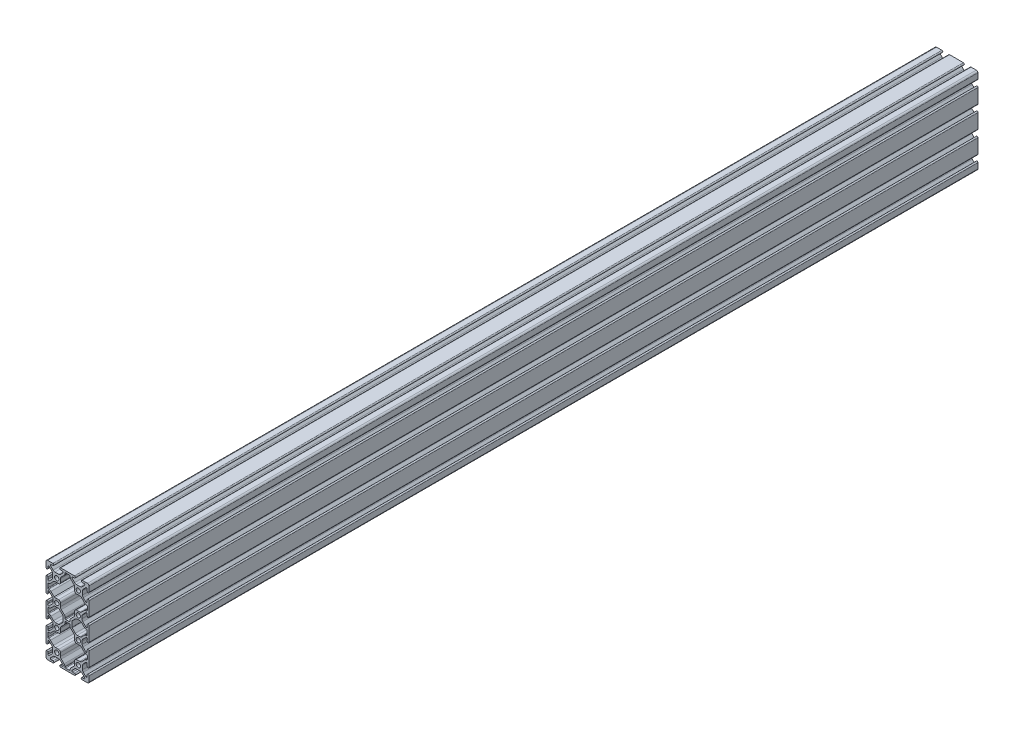
SolidWorks part; units mm, degrees
material "6061 Alloy"
ref_plane "Front Plane" through (0, 0, 0) normal (0, 0, 1) x (1, 0, 0)
ref_plane "Top Plane" through (0, 0, 0) normal (0, 1, 0) x (1, 0, 0)
ref_plane "Right Plane" through (0, 0, 0) normal (1, 0, 0) x (0, 0, -1)
sketch "Sketch1" plane through (0, 0, 0) normal (0, 0, 1) x (1, 0, 0)
  line L0 (-25.6036, 0) -> (0, 0) construction
  line L1 (-8.2025, 43.3108) -> (-5.2383, 46.275)
  line L2 (-25, 3.77) -> (-25, -3.77)
  line L3 (-8.1858, 12.4875) -> (-8.1858, 11.0114)
  line L4 (8.1878, 11.0114) -> (8.1878, 14.5891)
  line L5 (3.7569, 4.9667) -> (7.2705, 8.4802)
  line L6 (14.3225, 16.7991) -> (10.3978, 16.7991)
  line L7 (15.6024, 17.1021) -> (19.2982, 20.7979)
  line L8 (22.1127, 21.7264) -> (21.5397, 21.7264)
  line L9 (-2.3158, 50) -> (2.3158, 50)
  line L10 (22.8749, 26.8568) -> (22.8749, 22.4886)
  line L11 (21.8715, 27.6122) -> (22.1256, 27.6122)
  line L12 (19.7762, 28.7106) -> (16.3874, 32.0994)
  line L13 (13.8398, 33.0305) -> (10.3624, 33.0305)
  line L14 (8.1524, 39.0512) -> (8.1524, 35.2405)
  line L15 (7.2223, 41.2645) -> (4.0122, 44.4746)
  line L16 (3.0895, 47.0978) -> (3.0895, 46.7023)
  line L17 (-22.86, 2.484) -> (-22.86, -2.484)
  line L18 (-5.137, 3.0639) -> (-5.137, -3.0639)
  line L19 (5.137, 3.0639) -> (5.137, -3.0639)
  line L20 (22.86, 2.484) -> (22.86, -2.484)
  line L21 (-5.328, 3.5248) -> (-8.9952, 7.192)
  line L22 (-14.0474, 8.1222) -> (-11.2408, 8.1222)
  line L23 (-16.2931, 7.192) -> (-19.3292, 4.1559)
  line L24 (25, 3.77) -> (25, -3.77)
  line L25 (-22.0978, 3.2462) -> (-21.8437, 3.2462)
  line L26 (-10.3899, 33.0305) -> (-10.3624, 33.0305)
  line L27 (-8.1858, 12.4875) -> (-8.1858, 14.5891)
  line L28 (-8.1524, 39.0512) -> (-8.1524, 35.2405)
  line L29 (-25.6036, -25) -> (3.1162, -25) construction
  line L30 (-12.5, -37.5) -> (-12.5, -51.8721) construction
  line L31 (8.2025, -43.3108) -> (5.2383, -46.275)
  line L32 (-2.8325, -2.6943) -> (-2.8325, -1.8197)
  line L33 (-2.0703, -1.0575) -> (2.0723, -1.0575)
  line L34 (2.8345, -2.6943) -> (2.8345, -1.8197)
  line L35 (-3.7549, -4.9667) -> (-7.2685, -8.4802)
  line L36 (-14.3205, -16.7991) -> (-10.3958, -16.7991)
  line L37 (-15.6004, -17.1021) -> (-19.2962, -20.7979)
  line L38 (-22.1107, -21.7264) -> (-21.5377, -21.7264)
  line L39 (-22.8729, -26.8568) -> (-22.8729, -22.4886)
  line L40 (-22.1107, -27.619) -> (-21.8566, -27.619)
  line L41 (5.328, -3.5248) -> (8.9952, -7.192)
  line L42 (11.2408, -8.1222) -> (14.0474, -8.1222)
  line L43 (16.2931, -7.192) -> (19.3292, -4.1559)
  line L44 (-19.7762, -28.7106) -> (-16.3874, -32.0994)
  line L45 (22.0978, -3.2462) -> (21.8437, -3.2462)
  line L46 (-13.8398, -33.0305) -> (-10.3899, -33.0305)
  line L47 (-7.2223, -41.2645) -> (-4.0122, -44.4746)
  line L48 (5.8948, -47.86) -> (8.0244, -47.86)
  line L49 (-8.0244, 50) -> (-2.3158, 50)
  line L50 (-8.0244, 47.86) -> (-5.8948, 47.86)
  line L51 (0, 47.86) -> (2.3273, 47.86)
  line L52 (-3.0895, -47.0978) -> (-3.0895, -46.7023)
  line L53 (-14.7082, 42.4485) -> (-10.2843, 42.4484)
  line L54 (-16.7975, 43.3108) -> (-19.7617, 46.275)
  line L55 (-19.1052, 47.86) -> (-16.9756, 47.86)
  line L56 (-23.0411, 50) -> (-16.9756, 50)
  line L57 (2.3158, 50) -> (8.0244, 50)
  line L58 (-25, 42.0822) -> (-25, 48.3182)
  line L59 (10.2843, -42.4484) -> (14.7082, -42.4485)
  line L60 (-22.86, 42.0822) -> (-22.86, 44.2118)
  line L61 (-21.1643, 44.6511) -> (-18.3279, 41.8147)
  line L62 (-17.3977, 39.5691) -> (-17.3977, 35.4309)
  line L63 (-18.3279, 33.1853) -> (-21.1271, 30.3861)
  line L64 (-22.86, 31.1039) -> (-22.86, 33.4422)
  line L65 (-25, 33.4422) -> (-25, 29.299)
  line L66 (-25, 21.2197) -> (-25, 29.299)
  line L67 (-25, 17.0404) -> (-25, 21.2197)
  line L68 (-22.8665, 17.0958) -> (-22.8665, 19.4894)
  line L69 (-21.2483, 19.7351) -> (-17.927, 16.4138)
  line L70 (-16.865, 11.3738) -> (-16.865, 14.4803)
  line L71 (-17.7378, 8.7737) -> (-21.0608, 5.4507)
  line L72 (-22.8659, 6.4893) -> (-22.8659, 8.2661)
  line L73 (-25, 3.77) -> (-25, 8.2776)
  line L74 (16.7975, -43.3108) -> (19.7617, -46.275)
  line L75 (19.1052, -47.86) -> (16.9756, -47.86)
  line L76 (16.9756, -50) -> (21.7588, -50)
  line L77 (21.7588, -50) -> (23.0411, -50)
  line L78 (25, -42.0822) -> (25, -48.3182)
  line L79 (22.86, -42.0822) -> (22.86, -44.2118)
  line L80 (21.1643, -44.6511) -> (18.3279, -41.8147)
  line L81 (17.3977, -39.5691) -> (17.3977, -35.4309)
  line L82 (18.3279, -33.1853) -> (21.1271, -30.3861)
  line L83 (25, -33.4422) -> (25, -29.299)
  line L84 (22.86, -31.1039) -> (22.86, -33.4422)
  line L85 (-2.3273, -47.86) -> (0, -47.86)
  line L86 (22.8665, -17.0958) -> (22.8665, -19.4894)
  line L87 (21.2483, -19.7351) -> (17.927, -16.4138)
  line L88 (16.865, -11.3738) -> (16.865, -14.4803)
  line L89 (17.7378, -8.7737) -> (21.0608, -5.4507)
  line L90 (22.8659, -6.4893) -> (22.8659, -8.2661)
  line L91 (25, -21.2197) -> (25, -29.299)
  line L92 (25, -17.0404) -> (25, -21.2197)
  line L93 (25, -3.77) -> (25, -8.2776)
  line L94 (-25, -3.77) -> (-25, -8.2776)
  line L95 (-12.5, 37.5) -> (-12.5, 51.8721) construction
  line L96 (-25.6036, 25) -> (3.1162, 25) construction
  line L97 (-22.8659, -6.4893) -> (-22.8659, -8.2661)
  line L98 (-17.7378, -8.7737) -> (-21.0608, -5.4507)
  line L99 (-16.865, -11.3738) -> (-16.865, -14.4803)
  line L100 (-21.2483, -19.7351) -> (-17.927, -16.4138)
  line L101 (-22.8665, -17.0958) -> (-22.8665, -19.4894)
  line L102 (-25, -17.0404) -> (-25, -21.2197)
  line L103 (-25, -21.2197) -> (-25, -29.299)
  line L104 (-25, -33.4422) -> (-25, -29.299)
  line L105 (-22.86, -31.1039) -> (-22.86, -33.4422)
  line L106 (25, 3.77) -> (25, 8.2776)
  line L107 (25, 17.0404) -> (25, 21.2197)
  line L108 (-18.3279, -33.1853) -> (-21.1271, -30.3861)
  line L109 (-17.3977, -39.5691) -> (-17.3977, -35.4309)
  line L110 (-21.1643, -44.6511) -> (-18.3279, -41.8147)
  line L111 (-22.86, -42.0822) -> (-22.86, -44.2118)
  line L112 (-25, -42.0822) -> (-25, -48.3182)
  line L113 (25, 21.2197) -> (25, 29.299)
  line L114 (2.3158, -50) -> (8.0244, -50)
  line L115 (-23.0411, -50) -> (-16.9756, -50)
  line L116 (22.8659, 6.4893) -> (22.8659, 8.2661)
  line L117 (17.7378, 8.7737) -> (21.0608, 5.4507)
  line L118 (16.865, 11.3738) -> (16.865, 14.4803)
  line L119 (21.2483, 19.7351) -> (17.927, 16.4138)
  line L120 (22.8665, 17.0958) -> (22.8665, 19.4894)
  line L121 (-2.3273, 47.86) -> (0, 47.86)
  line L122 (22.86, 31.1039) -> (22.86, 33.4422)
  line L123 (25, 33.4422) -> (25, 29.299)
  line L124 (-19.1052, -47.86) -> (-16.9756, -47.86)
  line L125 (18.3279, 33.1853) -> (21.1271, 30.3861)
  line L126 (17.3977, 39.5691) -> (17.3977, 35.4309)
  line L127 (21.1643, 44.6511) -> (18.3279, 41.8147)
  line L128 (22.86, 42.0822) -> (22.86, 44.2118)
  line L129 (25, 42.0822) -> (25, 48.3182)
  line L130 (-16.7975, -43.3108) -> (-19.7617, -46.275)
  line L131 (21.7588, 50) -> (23.0411, 50)
  line L132 (16.9756, 50) -> (21.7588, 50)
  line L133 (19.1052, 47.86) -> (16.9756, 47.86)
  line L134 (16.7975, 43.3108) -> (19.7617, 46.275)
  line L135 (10.2843, 42.4484) -> (14.7082, 42.4485)
  line L136 (-14.7082, -42.4485) -> (-10.2843, -42.4484)
  line L137 (-3.0895, 47.0978) -> (-3.0895, 46.7023)
  line L138 (5.8948, 47.86) -> (8.0244, 47.86)
  line L139 (0, -47.86) -> (2.3273, -47.86)
  line L140 (-8.0244, -47.86) -> (-5.8948, -47.86)
  line L141 (-8.0244, -50) -> (-2.3158, -50)
  line L142 (-8.1524, -39.0512) -> (-8.1524, -35.2405)
  line L143 (-8.1858, -12.4875) -> (-8.1858, -14.5891)
  line L144 (-10.3899, -33.0305) -> (-10.3624, -33.0305)
  line L145 (-22.0978, -3.2462) -> (-21.8437, -3.2462)
  line L146 (-16.2931, -7.192) -> (-19.3292, -4.1559)
  line L147 (-14.0474, -8.1222) -> (-11.2408, -8.1222)
  line L148 (-5.328, -3.5248) -> (-8.9952, -7.192)
  line L149 (3.0895, -47.0978) -> (3.0895, -46.7023)
  line L150 (7.2223, -41.2645) -> (4.0122, -44.4746)
  line L151 (8.1524, -39.0512) -> (8.1524, -35.2405)
  line L152 (13.8398, -33.0305) -> (10.3624, -33.0305)
  line L153 (19.7762, -28.7106) -> (16.3874, -32.0994)
  line L154 (-7.2223, 41.2645) -> (-4.0122, 44.4746)
  line L155 (21.8715, -27.6122) -> (22.1256, -27.6122)
  line L156 (22.8749, -26.8568) -> (22.8749, -22.4886)
  line L157 (-2.3158, -50) -> (2.3158, -50)
  line L158 (22.1127, -21.7264) -> (21.5397, -21.7264)
  line L159 (15.6024, -17.1021) -> (19.2982, -20.7979)
  line L160 (-13.8398, 33.0305) -> (-10.3899, 33.0305)
  line L161 (14.3225, -16.7991) -> (10.3978, -16.7991)
  line L162 (22.0978, 3.2462) -> (21.8437, 3.2462)
  line L163 (-19.7762, 28.7106) -> (-16.3874, 32.0994)
  line L164 (16.2931, 7.192) -> (19.3292, 4.1559)
  line L165 (11.2408, 8.1222) -> (14.0474, 8.1222)
  line L166 (5.328, 3.5248) -> (8.9952, 7.192)
  line L167 (3.7569, -4.9667) -> (7.2705, -8.4802)
  line L168 (8.1878, -11.0114) -> (8.1878, -14.5891)
  line L169 (-8.1858, -12.4875) -> (-8.1858, -11.0114)
  line L170 (-8.2025, -43.3108) -> (-5.2383, -46.275)
  line L171 (-22.1107, 27.619) -> (-21.8566, 27.619)
  line L172 (-22.8729, 26.8568) -> (-22.8729, 22.4886)
  line L173 (-22.1107, 21.7264) -> (-21.5377, 21.7264)
  line L174 (-15.6004, 17.1021) -> (-19.2962, 20.7979)
  line L175 (-14.3205, 16.7991) -> (-10.3958, 16.7991)
  line L176 (-3.7549, 4.9667) -> (-7.2685, 8.4802)
  line L177 (2.8345, 2.6943) -> (2.8345, 1.8197)
  line L178 (-2.0703, 1.0575) -> (2.0723, 1.0575)
  line L179 (-2.8325, 2.6943) -> (-2.8325, 1.8197)
  line L180 (25, 0) -> (0, 0) construction
  line L184 (8.2025, 43.3108) -> (5.2383, 46.275)
  arc A0 (-8.1858, 14.5891) -> (-10.3958, 16.7991) centre (-10.3958, 14.5891) ccw
  arc A1 (-8.1524, 35.2405) -> (-10.3624, 33.0305) centre (-10.3624, 35.2405) cw
  arc A2 (10.3978, 16.7991) -> (8.1878, 14.5891) centre (10.3978, 14.5891) ccw
  circle A3 centre (-12.5, 12.5) radius 2.5
  circle A4 centre (-12.5, 37.5) radius 2.5
  arc A5 (7.2705, 8.4802) -> (8.1878, 11.0114) centre (5.0248, 10.7259) ccw
  arc A6 (10.3624, 33.0305) -> (8.1524, 35.2405) centre (10.3624, 35.2405) cw
  arc A7 (14.3225, 16.7991) -> (15.6024, 17.1021) centre (14.2466, 19.974) ccw
  arc A8 (21.5397, 21.7264) -> (19.2982, 20.7979) centre (21.5397, 18.5564) ccw
  arc A9 (22.1127, 21.7264) -> (22.8749, 22.4886) centre (22.1127, 22.4886) ccw
  arc A10 (22.8749, 26.8568) -> (22.1256, 27.6122) centre (22.1127, 26.8501) ccw
  arc A11 (-8.0244, 47.86) -> (-8.0244, 50) centre (-8.0244, 48.93) cw
  arc A12 (19.7762, 28.7106) -> (21.8715, 27.6122) centre (22.1894, 30.7662) ccw
  arc A13 (16.3874, 32.0994) -> (13.8398, 33.0305) centre (13.8398, 29.0797) ccw
  circle A14 centre (12.5, -12.5) radius 2.5
  arc A15 (8.1524, 39.0512) -> (7.2223, 41.2645) centre (4.9767, 39.0188) ccw
  arc A16 (3.0895, 47.0978) -> (2.3273, 47.86) centre (2.3273, 47.0978) ccw
  arc A17 (3.0895, 46.7023) -> (4.0122, 44.4746) centre (6.2399, 46.7023) ccw
  arc A18 (-3.0895, 47.0978) -> (-2.3273, 47.86) centre (-2.3273, 47.0978) cw
  circle A19 centre (12.5, -37.5) radius 2.5
  arc A20 (-3.7549, -4.9667) -> (-2.8325, -2.6943) centre (-5.9826, -2.739) ccw
  arc A21 (-5.137, 3.0639) -> (-5.328, 3.5248) centre (-5.7889, 3.0639) ccw
  arc A22 (-8.9952, 7.192) -> (-11.2408, 8.1222) centre (-11.2408, 4.9464) ccw
  arc A23 (-14.0474, 8.1222) -> (-16.2931, 7.192) centre (-14.0474, 4.9464) ccw
  arc A24 (-21.8437, 3.2462) -> (-19.3292, 4.1559) centre (-21.5569, 6.3836) ccw
  arc A25 (-22.0978, 3.2462) -> (-22.86, 2.484) centre (-22.0978, 2.484) ccw
  arc A26 (-2.0703, -1.0575) -> (-2.8325, -1.8197) centre (-2.0703, -1.8197) ccw
  arc A27 (2.0723, -1.0575) -> (2.8345, -1.8197) centre (2.0723, -1.8197) cw
  arc A28 (3.7569, -4.9667) -> (2.8345, -2.6943) centre (5.9846, -2.739) cw
  arc A29 (-7.2685, -8.4802) -> (-8.1858, -11.0114) centre (-5.0228, -10.7259) ccw
  arc A30 (8.0244, -47.86) -> (8.0244, -50) centre (8.0244, -48.93) cw
  arc A31 (-14.3205, -16.7991) -> (-15.6004, -17.1021) centre (-14.2446, -19.974) ccw
  arc A32 (-21.5377, -21.7264) -> (-19.2962, -20.7979) centre (-21.5377, -18.5564) ccw
  arc A33 (-22.1107, -21.7264) -> (-22.8729, -22.4886) centre (-22.1107, -22.4886) ccw
  arc A34 (-22.8729, -26.8568) -> (-22.1107, -27.619) centre (-22.1107, -26.8568) ccw
  arc A35 (-19.7762, -28.7106) -> (-21.8566, -27.619) centre (-22.1844, -30.772) ccw
  arc A36 (-16.3874, -32.0994) -> (-13.8398, -33.0305) centre (-13.8398, -29.0797) ccw
  arc A37 (5.137, -3.0639) -> (5.328, -3.5248) centre (5.7889, -3.0639) ccw
  arc A38 (8.9952, -7.192) -> (11.2408, -8.1222) centre (11.2408, -4.9464) ccw
  arc A39 (14.0474, -8.1222) -> (16.2931, -7.192) centre (14.0474, -4.9464) ccw
  arc A40 (21.8437, -3.2462) -> (19.3292, -4.1559) centre (21.5569, -6.3836) ccw
  arc A41 (22.0978, -3.2462) -> (22.86, -2.484) centre (22.0978, -2.484) ccw
  arc A42 (5.8948, -47.86) -> (5.2383, -46.275) centre (5.8948, -46.9315) cw
  arc A43 (-8.1524, -39.0512) -> (-7.2223, -41.2645) centre (-4.9767, -39.0188) ccw
  arc A44 (10.2843, -42.4484) -> (8.2025, -43.3108) centre (10.2843, -45.3926) ccw
  arc A45 (16.7975, -43.3108) -> (14.7082, -42.4485) centre (14.7157, -45.3926) ccw
  arc A46 (19.1052, -47.86) -> (19.7617, -46.275) centre (19.1052, -46.9315) ccw
  arc A47 (16.9756, -47.86) -> (16.9756, -50) centre (16.9756, -48.93) ccw
  arc A48 (-5.8948, 47.86) -> (-5.2383, 46.275) centre (-5.8948, 46.9315) cw
  arc A49 (-3.0895, 46.7023) -> (-4.0122, 44.4746) centre (-6.2399, 46.7023) cw
  arc A50 (-10.2843, 42.4484) -> (-8.2025, 43.3108) centre (-10.2843, 45.3926) ccw
  arc A51 (-16.7975, 43.3108) -> (-14.7082, 42.4485) centre (-14.7157, 45.3926) ccw
  arc A52 (-19.1052, 47.86) -> (-19.7617, 46.275) centre (-19.1052, 46.9315) ccw
  arc A53 (-16.9756, 47.86) -> (-16.9756, 50) centre (-16.9756, 48.93) ccw
  arc A54 (-23.0411, 50) -> (-25, 48.3182) centre (-23.0411, 48.0183) ccw
  arc A55 (-25, 42.0822) -> (-22.86, 42.0822) centre (-23.93, 42.0822) ccw
  arc A56 (-21.1643, 44.6511) -> (-22.86, 44.2118) centre (-21.8829, 43.9325) ccw
  arc A57 (-17.3977, 39.5691) -> (-18.3279, 41.8147) centre (-20.5736, 39.5691) ccw
  arc A58 (-18.3279, 33.1853) -> (-17.3977, 35.4309) centre (-20.5736, 35.4309) ccw
  arc A59 (-22.86, 31.1039) -> (-21.1271, 30.3861) centre (-21.8449, 31.1039) ccw
  arc A60 (-22.86, 33.4422) -> (-25, 33.4422) centre (-23.93, 33.4422) ccw
  arc A61 (-25, 17.0404) -> (-22.8665, 17.0958) centre (-23.9321, 17.0236) ccw
  arc A62 (-21.2483, 19.7351) -> (-22.8665, 19.4894) centre (-21.9669, 19.0165) ccw
  arc A63 (-16.865, 14.4803) -> (-17.927, 16.4138) centre (-20.0063, 14.0133) ccw
  arc A64 (-17.7378, 8.7737) -> (-16.865, 11.3738) centre (-20.017, 10.9853) ccw
  arc A65 (-22.8659, 6.4893) -> (-21.0608, 5.4507) centre (-21.9633, 5.97) ccw
  arc A66 (-22.8659, 8.2661) -> (-25, 8.2776) centre (-23.9329, 8.2719) ccw
  arc A67 (23.0411, -50) -> (25, -48.3182) centre (23.0411, -48.0183) ccw
  arc A68 (25, -42.0822) -> (22.86, -42.0822) centre (23.93, -42.0822) ccw
  arc A69 (21.1643, -44.6511) -> (22.86, -44.2118) centre (21.8829, -43.9325) ccw
  arc A70 (17.3977, -39.5691) -> (18.3279, -41.8147) centre (20.5736, -39.5691) ccw
  arc A71 (18.3279, -33.1853) -> (17.3977, -35.4309) centre (20.5736, -35.4309) ccw
  arc A72 (22.86, -31.1039) -> (21.1271, -30.3861) centre (21.8449, -31.1039) ccw
  arc A73 (22.86, -33.4422) -> (25, -33.4422) centre (23.93, -33.4422) ccw
  arc A74 (25, -17.0404) -> (22.8665, -17.0958) centre (23.9321, -17.0236) ccw
  arc A75 (21.2483, -19.7351) -> (22.8665, -19.4894) centre (21.9669, -19.0165) ccw
  arc A76 (16.865, -14.4803) -> (17.927, -16.4138) centre (20.0063, -14.0133) ccw
  arc A77 (17.7378, -8.7737) -> (16.865, -11.3738) centre (20.017, -10.9853) ccw
  arc A78 (22.8659, -6.4893) -> (21.0608, -5.4507) centre (21.9633, -5.97) ccw
  arc A79 (22.8659, -8.2661) -> (25, -8.2776) centre (23.9329, -8.2719) ccw
  arc A80 (-22.8659, -8.2661) -> (-25, -8.2776) centre (-23.9329, -8.2719) cw
  arc A81 (-22.8659, -6.4893) -> (-21.0608, -5.4507) centre (-21.9633, -5.97) cw
  arc A82 (-17.7378, -8.7737) -> (-16.865, -11.3738) centre (-20.017, -10.9853) cw
  arc A83 (-16.865, -14.4803) -> (-17.927, -16.4138) centre (-20.0063, -14.0133) cw
  arc A84 (-21.2483, -19.7351) -> (-22.8665, -19.4894) centre (-21.9669, -19.0165) cw
  arc A85 (-25, -17.0404) -> (-22.8665, -17.0958) centre (-23.9321, -17.0236) cw
  arc A86 (-22.86, -33.4422) -> (-25, -33.4422) centre (-23.93, -33.4422) cw
  arc A87 (-22.86, -31.1039) -> (-21.1271, -30.3861) centre (-21.8449, -31.1039) cw
  arc A88 (-18.3279, -33.1853) -> (-17.3977, -35.4309) centre (-20.5736, -35.4309) cw
  arc A89 (-17.3977, -39.5691) -> (-18.3279, -41.8147) centre (-20.5736, -39.5691) cw
  arc A90 (-21.1643, -44.6511) -> (-22.86, -44.2118) centre (-21.8829, -43.9325) cw
  arc A91 (-25, -42.0822) -> (-22.86, -42.0822) centre (-23.93, -42.0822) cw
  arc A92 (-23.0411, -50) -> (-25, -48.3182) centre (-23.0411, -48.0183) cw
  arc A93 (22.8659, 8.2661) -> (25, 8.2776) centre (23.9329, 8.2719) cw
  arc A94 (22.8659, 6.4893) -> (21.0608, 5.4507) centre (21.9633, 5.97) cw
  arc A95 (17.7378, 8.7737) -> (16.865, 11.3738) centre (20.017, 10.9853) cw
  arc A96 (16.865, 14.4803) -> (17.927, 16.4138) centre (20.0063, 14.0133) cw
  arc A97 (21.2483, 19.7351) -> (22.8665, 19.4894) centre (21.9669, 19.0165) cw
  arc A98 (25, 17.0404) -> (22.8665, 17.0958) centre (23.9321, 17.0236) cw
  arc A99 (22.86, 33.4422) -> (25, 33.4422) centre (23.93, 33.4422) cw
  arc A100 (22.86, 31.1039) -> (21.1271, 30.3861) centre (21.8449, 31.1039) cw
  arc A101 (18.3279, 33.1853) -> (17.3977, 35.4309) centre (20.5736, 35.4309) cw
  arc A102 (17.3977, 39.5691) -> (18.3279, 41.8147) centre (20.5736, 39.5691) cw
  arc A103 (21.1643, 44.6511) -> (22.86, 44.2118) centre (21.8829, 43.9325) cw
  arc A104 (25, 42.0822) -> (22.86, 42.0822) centre (23.93, 42.0822) cw
  arc A105 (23.0411, 50) -> (25, 48.3182) centre (23.0411, 48.0183) cw
  arc A106 (16.9756, 47.86) -> (16.9756, 50) centre (16.9756, 48.93) cw
  arc A107 (19.1052, 47.86) -> (19.7617, 46.275) centre (19.1052, 46.9315) cw
  arc A108 (16.7975, 43.3108) -> (14.7082, 42.4485) centre (14.7157, 45.3926) cw
  arc A109 (10.2843, 42.4484) -> (8.2025, 43.3108) centre (10.2843, 45.3926) cw
  arc A110 (-8.1524, 39.0512) -> (-7.2223, 41.2645) centre (-4.9767, 39.0188) cw
  arc A111 (5.8948, 47.86) -> (5.2383, 46.275) centre (5.8948, 46.9315) ccw
  arc A112 (-16.9756, -47.86) -> (-16.9756, -50) centre (-16.9756, -48.93) cw
  arc A113 (-19.1052, -47.86) -> (-19.7617, -46.275) centre (-19.1052, -46.9315) cw
  arc A114 (-16.7975, -43.3108) -> (-14.7082, -42.4485) centre (-14.7157, -45.3926) cw
  arc A115 (-10.2843, -42.4484) -> (-8.2025, -43.3108) centre (-10.2843, -45.3926) cw
  arc A116 (-3.0895, -46.7023) -> (-4.0122, -44.4746) centre (-6.2399, -46.7023) ccw
  arc A117 (-5.8948, -47.86) -> (-5.2383, -46.275) centre (-5.8948, -46.9315) ccw
  arc A118 (-22.0978, -3.2462) -> (-22.86, -2.484) centre (-22.0978, -2.484) cw
  arc A119 (-21.8437, -3.2462) -> (-19.3292, -4.1559) centre (-21.5569, -6.3836) cw
  arc A120 (-14.0474, -8.1222) -> (-16.2931, -7.192) centre (-14.0474, -4.9464) cw
  arc A121 (-8.9952, -7.192) -> (-11.2408, -8.1222) centre (-11.2408, -4.9464) cw
  arc A122 (-5.137, -3.0639) -> (-5.328, -3.5248) centre (-5.7889, -3.0639) cw
  arc A123 (-3.0895, -47.0978) -> (-2.3273, -47.86) centre (-2.3273, -47.0978) ccw
  arc A124 (3.0895, -46.7023) -> (4.0122, -44.4746) centre (6.2399, -46.7023) cw
  arc A125 (3.0895, -47.0978) -> (2.3273, -47.86) centre (2.3273, -47.0978) cw
  arc A126 (8.1524, -39.0512) -> (7.2223, -41.2645) centre (4.9767, -39.0188) cw
  arc A127 (16.3874, -32.0994) -> (13.8398, -33.0305) centre (13.8398, -29.0797) cw
  arc A128 (19.7762, -28.7106) -> (21.8715, -27.6122) centre (22.1894, -30.7662) cw
  arc A129 (-8.0244, -47.86) -> (-8.0244, -50) centre (-8.0244, -48.93) ccw
  arc A130 (22.8749, -26.8568) -> (22.1256, -27.6122) centre (22.1127, -26.8501) cw
  arc A131 (22.1127, -21.7264) -> (22.8749, -22.4886) centre (22.1127, -22.4886) cw
  arc A132 (21.5397, -21.7264) -> (19.2982, -20.7979) centre (21.5397, -18.5564) cw
  arc A133 (14.3225, -16.7991) -> (15.6024, -17.1021) centre (14.2466, -19.974) cw
  arc A134 (22.0978, 3.2462) -> (22.86, 2.484) centre (22.0978, 2.484) cw
  arc A135 (21.8437, 3.2462) -> (19.3292, 4.1559) centre (21.5569, 6.3836) cw
  arc A136 (14.0474, 8.1222) -> (16.2931, 7.192) centre (14.0474, 4.9464) cw
  arc A137 (8.9952, 7.192) -> (11.2408, 8.1222) centre (11.2408, 4.9464) cw
  arc A138 (5.137, 3.0639) -> (5.328, 3.5248) centre (5.7889, 3.0639) cw
  arc A139 (10.3624, -33.0305) -> (8.1524, -35.2405) centre (10.3624, -35.2405) ccw
  arc A140 (7.2705, -8.4802) -> (8.1878, -11.0114) centre (5.0248, -10.7259) cw
  circle A141 centre (-12.5, -37.5) radius 2.5
  arc A142 (-16.3874, 32.0994) -> (-13.8398, 33.0305) centre (-13.8398, 29.0797) cw
  arc A143 (-19.7762, 28.7106) -> (-21.8566, 27.619) centre (-22.1844, 30.772) cw
  arc A144 (-22.8729, 26.8568) -> (-22.1107, 27.619) centre (-22.1107, 26.8568) cw
  arc A145 (-22.1107, 21.7264) -> (-22.8729, 22.4886) centre (-22.1107, 22.4886) cw
  arc A146 (-21.5377, 21.7264) -> (-19.2962, 20.7979) centre (-21.5377, 18.5564) cw
  arc A147 (-14.3205, 16.7991) -> (-15.6004, 17.1021) centre (-14.2446, 19.974) cw
  arc A148 (8.0244, 47.86) -> (8.0244, 50) centre (8.0244, 48.93) ccw
  circle A149 centre (-12.5, -12.5) radius 2.5
  arc A150 (-7.2685, 8.4802) -> (-8.1858, 11.0114) centre (-5.0228, 10.7259) cw
  arc A151 (3.7569, 4.9667) -> (2.8345, 2.6943) centre (5.9846, 2.739) ccw
  arc A152 (2.0723, 1.0575) -> (2.8345, 1.8197) centre (2.0723, 1.8197) ccw
  arc A153 (-2.0703, 1.0575) -> (-2.8325, 1.8197) centre (-2.0703, 1.8197) cw
  arc A154 (-3.7549, 4.9667) -> (-2.8325, 2.6943) centre (-5.9826, 2.739) cw
  circle A155 centre (12.5, 37.5) radius 2.5
  circle A156 centre (12.5, 12.5) radius 2.5
  arc A157 (10.3978, -16.7991) -> (8.1878, -14.5891) centre (10.3978, -14.5891) cw
  arc A158 (-8.1524, -35.2405) -> (-10.3624, -33.0305) centre (-10.3624, -35.2405) ccw
  arc A159 (-8.1858, -14.5891) -> (-10.3958, -16.7991) centre (-10.3958, -14.5891) cw
  point P0 (-5.137, 0)
  point P2 (-25, 0)
  point P3 (-22.86, 0)
  point P5 (5.137, 0)
  point P511 (22.86, 0)
  dimension "D3" = 6.5
  dimension "D4" = 14.86
  dimension "D6" = 5
  dimension "D7" = 25
  dimension "D10" = 2.21
  dimension "D12" = 2.14
  dimension "D2" = 0.7622
  dimension "D5" = 0.7622
  dimension "D8" = 2.21
  dimension "D11" = 2.21
  dimension "D13" = 2.21
  dimension "D14" = 3.17
  dimension "D15" = 3.17
  dimension "D16" = 3.17
  dimension "D17" = 3.17
  dimension "D9" = 2.14
  dimension "D18" = 100
  dimension "D19" = 50
extrude "Extrude1" add sketch "Sketch1" against normal blind 1031.646
